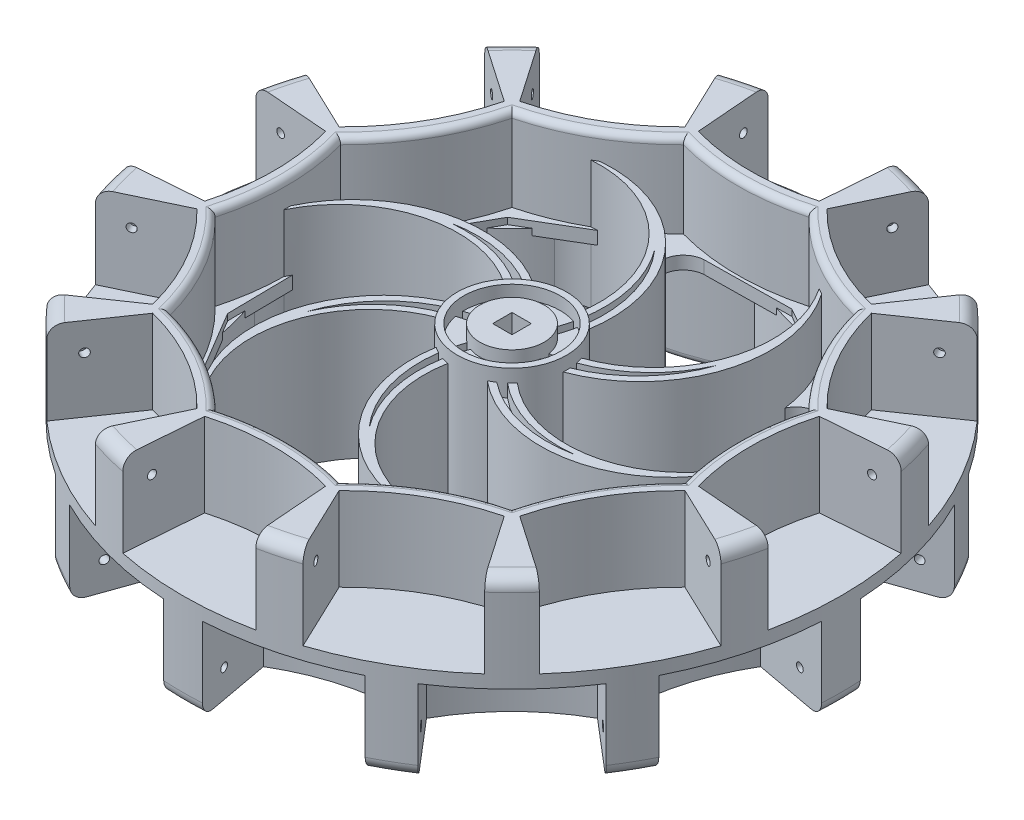
SolidWorks part; units mm, degrees
material "Nylon 101"
ref_plane "Front Plane" through (0, 0, 0) normal (0, 0, 1) x (1, 0, 0)
ref_plane "Top Plane" through (0, 0, 0) normal (0, 1, 0) x (1, 0, 0)
ref_plane "Right Plane" through (0, 0, 0) normal (1, 0, 0) x (0, 0, -1)
sketch "Sketch1" plane through (0, 0, 0) normal (0, 1, 0) x (1, 0, 0)
  line L1 (-28.2843, -28.2843) -> (-10.3528, -38.637) construction
  line L2 (-10.3528, -38.637) -> (10.3528, -38.637) construction
  line L3 (10.3528, -38.637) -> (28.2843, -28.2843) construction
  line L4 (28.2843, -28.2843) -> (38.637, -10.3528) construction
  line L5 (38.637, -10.3528) -> (38.637, 10.3528) construction
  line L6 (38.637, 10.3528) -> (28.2843, 28.2843) construction
  line L7 (28.2843, 28.2843) -> (10.3528, 38.637) construction
  line L8 (10.3528, 38.637) -> (-10.3528, 38.637) construction
  line L9 (-10.3528, 38.637) -> (-28.2843, 28.2843) construction
  line L10 (-28.2843, 28.2843) -> (-38.637, 10.3528) construction
  line L11 (-38.637, 10.3528) -> (-38.637, -10.3528) construction
  line L12 (-38.637, -10.3528) -> (-28.2843, -28.2843) construction
  circle A0 centre (0, 0) radius 38.637 construction
  arc A1 (38.637, 10.3528) -> (38.637, -10.3528) centre (71.5246, 0) ccw
  arc A2 (38.637, -10.3528) -> (28.2843, -28.2843) centre (61.9421, -35.7623) ccw
  arc A3 (28.2843, -28.2843) -> (10.3528, -38.637) centre (35.7623, -61.9421) ccw
  arc A4 (10.3528, -38.637) -> (-10.3528, -38.637) centre (0, -71.5246) ccw
  arc A5 (-10.3528, -38.637) -> (-28.2843, -28.2843) centre (-35.7623, -61.9421) ccw
  arc A6 (-28.2843, -28.2843) -> (-38.637, -10.3528) centre (-61.9421, -35.7623) ccw
  arc A7 (-38.637, -10.3528) -> (-38.637, 10.3528) centre (-71.5246, 0) ccw
  arc A8 (-38.637, 10.3528) -> (-28.2843, 28.2843) centre (-61.9421, 35.7623) ccw
  arc A9 (-28.2843, 28.2843) -> (-10.3528, 38.637) centre (-35.7623, 61.9421) ccw
  arc A10 (-10.3528, 38.637) -> (10.3528, 38.637) centre (0, 71.5246) ccw
  arc A11 (10.3528, 38.637) -> (28.2843, 28.2843) centre (35.7623, 61.9421) ccw
  arc A12 (28.2843, 28.2843) -> (38.637, 10.3528) centre (61.9421, 35.7623) ccw
  point P51 (0, 0)
  dimension "D2" = 34.4786
  dimension "D1" = 80
  dimension "D3" = 12
extrude "Boss-Extrude1" add sketch "Sketch1" along normal mid plane 28
sketch "Sketch3" plane through (0, 0, 0) normal (0, 1, 0) x (1, 0, 0)
  circle A0 centre (0, 0) radius 51.2
  dimension "D1" = 102.4
extrude "Boss-Extrude2" add sketch "Sketch3" along normal mid plane 2 contours A0
sketch "Sketch4" plane through (0, 14, 0) normal (0, 1, 0) x (1, 0, 0)
  arc A0 (9.7459, 36.372) -> (26.6262, 26.6262) centre (35.7623, 61.9421) ccw
  arc A1 (26.6262, 26.6262) -> (36.372, 9.7459) centre (61.9421, 35.7623) ccw
  arc A2 (36.372, 9.7459) -> (36.372, -9.7459) centre (71.5246, 0) ccw
  arc A3 (36.372, -9.7459) -> (26.6262, -26.6262) centre (61.9421, -35.7623) ccw
  arc A4 (26.6262, -26.6262) -> (9.7459, -36.372) centre (35.7623, -61.9421) ccw
  arc A5 (9.7459, -36.372) -> (-9.7459, -36.372) centre (0, -71.5246) ccw
  arc A6 (-9.7459, -36.372) -> (-26.6262, -26.6262) centre (-35.7623, -61.9421) ccw
  arc A7 (-26.6262, -26.6262) -> (-36.372, -9.7459) centre (-61.9421, -35.7623) ccw
  arc A8 (-36.372, -9.7459) -> (-36.372, 9.7459) centre (-71.5246, 0) ccw
  arc A9 (-36.372, 9.7459) -> (-26.6262, 26.6262) centre (-61.9421, 35.7623) ccw
  arc A10 (-26.6262, 26.6262) -> (-9.7459, 36.372) centre (-35.7623, 61.9421) ccw
  arc A11 (-9.7459, 36.372) -> (9.7459, 36.372) centre (0, 71.5246) ccw
  arc A12 (38.637, -10.3528) -> (28.2843, -28.2843) centre (61.9421, -35.7623) ccw
  arc A13 (38.637, 10.3528) -> (38.637, -10.3528) centre (71.5246, 0) ccw
  arc A14 (28.2843, 28.2843) -> (38.637, 10.3528) centre (61.9421, 35.7623) ccw
  arc A15 (10.3528, 38.637) -> (28.2843, 28.2843) centre (35.7623, 61.9421) ccw
  arc A16 (-10.3528, 38.637) -> (10.3528, 38.637) centre (0, 71.5246) ccw
  arc A17 (-28.2843, 28.2843) -> (-10.3528, 38.637) centre (-35.7623, 61.9421) ccw
  arc A18 (-38.637, 10.3528) -> (-28.2843, 28.2843) centre (-61.9421, 35.7623) ccw
  arc A19 (-38.637, -10.3528) -> (-38.637, 10.3528) centre (-71.5246, 0) ccw
  arc A20 (-28.2843, -28.2843) -> (-38.637, -10.3528) centre (-61.9421, -35.7623) ccw
  arc A21 (-10.3528, -38.637) -> (-28.2843, -28.2843) centre (-35.7623, -61.9421) ccw
  arc A22 (10.3528, -38.637) -> (-10.3528, -38.637) centre (0, -71.5246) ccw
  arc A23 (28.2843, -28.2843) -> (10.3528, -38.637) centre (35.7623, -61.9421) ccw
  arc A24 (38.637, -10.3528) -> (28.2843, -28.2843) centre (61.9421, -35.7623) ccw
  arc A25 (38.637, 10.3528) -> (38.637, -10.3528) centre (71.5246, 0) ccw
  arc A26 (28.2843, 28.2843) -> (38.637, 10.3528) centre (61.9421, 35.7623) ccw
  arc A27 (10.3528, 38.637) -> (28.2843, 28.2843) centre (35.7623, 61.9421) ccw
  arc A28 (-10.3528, 38.637) -> (10.3528, 38.637) centre (0, 71.5246) ccw
  arc A29 (-28.2843, 28.2843) -> (-10.3528, 38.637) centre (-35.7623, 61.9421) ccw
  arc A30 (-38.637, 10.3528) -> (-28.2843, 28.2843) centre (-61.9421, 35.7623) ccw
  arc A31 (-38.637, -10.3528) -> (-38.637, 10.3528) centre (-71.5246, 0) ccw
  arc A32 (-28.2843, -28.2843) -> (-38.637, -10.3528) centre (-61.9421, -35.7623) ccw
  arc A33 (-10.3528, -38.637) -> (-28.2843, -28.2843) centre (-35.7623, -61.9421) ccw
  arc A34 (10.3528, -38.637) -> (-10.3528, -38.637) centre (0, -71.5246) ccw
  arc A35 (28.2843, -28.2843) -> (10.3528, -38.637) centre (35.7623, -61.9421) ccw
  dimension "D1" = 0
  dimension "D2" = 2
extrude "Cut-Extrude1" cut sketch "Sketch4" against normal blind 4 contours A11 A10 A9 A8 A7 A6 A5 A4 A3 A2 A1 A0 region at (0, 14, 0)
mirror "Mirror1" about plane through (0, 0, 0) normal (0, 1, 0) of "Cut-Extrude1"
sketch "Sketch5" plane through (0, 10, 0) normal (0, 1, 0) x (1, 0, 0)
  circle A0 centre (0, 0) radius 5
  circle A1 centre (0, 0) radius 7.5
  circle A2 centre (0, 0) radius 8.5
  dimension "D1" = 10
  dimension "D2" = 15
  dimension "D3" = 1
extrude "Boss-Extrude3" add sketch "Sketch5" along normal blind 2 contours A2 A1 | A0 region at (0, 10, 0) region at (-8.2596, 10, 0)
mirror "Mirror2" about plane through (0, 0, 0) normal (0, 1, 0) of "Boss-Extrude3"
sketch "Sketch6" plane through (0, 12, 0) normal (0, 1, 0) x (1, 0, 0)
  line L1 (1.5, 1.5) -> (-1.5, 1.5)
  line L2 (1.5, 1.5) -> (1.5, -1.5)
  line L3 (1.5, -1.5) -> (-1.5, -1.5)
  line L4 (-1.5, 1.5) -> (-1.5, -1.5)
  line L5 (1.5, 1.5) -> (-1.5, -1.5) construction
  line L6 (1.5, -1.5) -> (-1.5, 1.5) construction
  point P0 (0, 0)
  dimension "D1" = 3
extrude "Cut-Extrude2" cut sketch "Sketch6" against normal through all
sketch "Sketch7" plane through (0, 10, 0) normal (0, 1, 0) x (1, 0, 0)
  line L1 (-3, -1.7321) -> (0, -3.4641) construction
  line L2 (0, -3.4641) -> (3, -1.7321) construction
  line L3 (3, -1.7321) -> (3, 1.7321) construction
  line L4 (3, 1.7321) -> (0, 3.4641) construction
  line L5 (0, 3.4641) -> (-3, 1.7321) construction
  line L6 (-3, 1.7321) -> (-3, -1.7321) construction
  circle A0 centre (0, 0) radius 3 construction
  circle A1 centre (0, 0) radius 8.5 construction
  arc A2 (6.4077, -5.5849) -> (5.7058, -6.3003) centre (0, 0) ccw
  circle A3 centre (0, 0) radius 5 construction
  arc A4 (4.6235, 1.9034) -> (7.3346, 37.8352) centre (1.8741, 20.179) ccw
  circle A5 centre (0, 0) radius 5
  arc A6 (4.7636, -1.5194) -> (7.3346, 37.8352) centre (1.4596, 18.4577) ccw
  arc A7 (3.9601, -3.0524) -> (36.4335, 12.5657) centre (18.4126, 8.4665) ccw
  arc A8 (1.066, -4.885) -> (36.4335, 12.5657) centre (16.7147, 7.9648) ccw
  arc A9 (-0.6634, -4.9558) -> (29.099, -25.2695) centre (16.5385, -11.7125) ccw
  arc A10 (-3.6976, -3.3657) -> (29.099, -25.2695) centre (15.2551, -10.4929) ccw
  arc A11 (-4.6235, -1.9034) -> (-7.3346, -37.8352) centre (-1.8741, -20.179) ccw
  arc A12 (-4.7636, 1.5194) -> (-7.3346, -37.8352) centre (-1.4596, -18.4577) ccw
  arc A13 (-3.9601, 3.0524) -> (-36.4335, -12.5657) centre (-18.4126, -8.4665) ccw
  arc A14 (-1.066, 4.885) -> (-36.4335, -12.5657) centre (-16.7147, -7.9648) ccw
  arc A15 (0.6634, 4.9558) -> (-29.099, 25.2695) centre (-16.5385, 11.7125) ccw
  arc A16 (3.6976, 3.3657) -> (-29.099, 25.2695) centre (-15.2551, 10.4929) ccw
  arc A17 (2.0852, -4.5444) -> (3.9056, -6.4029) centre (16.7147, 7.9648) ccw
  arc A18 (-10.3528, 38.637) -> (10.3528, 38.637) centre (0, 71.5246) ccw construction
  circle A19 centre (0, 0) radius 7.5 construction
  circle A20 centre (0, 0) radius 7.5
  arc A21 (2.0837, -2.1583) -> (2.1324, -2.2329) centre (18.4126, 8.4665) ccw
  arc A22 (0.8166, -2.8867) -> (0.8687, -2.9626) centre (16.7147, 7.9648) ccw
  arc A23 (-0.8273, -2.8837) -> (-0.8676, -2.9632) centre (16.5385, -11.7125) ccw
  arc A24 (-2.0917, -2.1506) -> (-2.1313, -2.2336) centre (15.2551, -10.4929) ccw
  arc A25 (-2.911, -0.7253) -> (-3, -0.7303) centre (-1.8741, -20.179) ccw
  arc A26 (-9.7459, 36.372) -> (9.7459, 36.372) centre (0, 71.5246) ccw
  arc A27 (-26.6262, 26.6262) -> (-9.7459, 36.372) centre (-35.7623, 61.9421) ccw
  arc A28 (-36.372, 9.7459) -> (-26.6262, 26.6262) centre (-61.9421, 35.7623) ccw
  arc A29 (-36.372, -9.7459) -> (-36.372, 9.7459) centre (-71.5246, 0) ccw
  arc A30 (-26.6262, -26.6262) -> (-36.372, -9.7459) centre (-61.9421, -35.7623) ccw
  arc A31 (-9.7459, -36.372) -> (-26.6262, -26.6262) centre (-35.7623, -61.9421) ccw
  arc A32 (9.7459, -36.372) -> (-9.7459, -36.372) centre (0, -71.5246) ccw
  arc A33 (26.6262, -26.6262) -> (9.7459, -36.372) centre (35.7623, -61.9421) ccw
  arc A34 (36.372, -9.7459) -> (26.6262, -26.6262) centre (61.9421, -35.7623) ccw
  arc A35 (36.372, 9.7459) -> (36.372, -9.7459) centre (71.5246, 0) ccw
  arc A36 (26.6262, 26.6262) -> (36.372, 9.7459) centre (61.9421, 35.7623) ccw
  arc A37 (9.7459, 36.372) -> (26.6262, 26.6262) centre (35.7623, 61.9421) ccw
  arc A38 (-9.7459, 36.372) -> (9.7459, 36.372) centre (0, 71.5246) ccw
  arc A39 (-26.6262, 26.6262) -> (-9.7459, 36.372) centre (-35.7623, 61.9421) ccw
  arc A40 (-36.372, 9.7459) -> (-26.6262, 26.6262) centre (-61.9421, 35.7623) ccw
  arc A41 (-36.372, -9.7459) -> (-36.372, 9.7459) centre (-71.5246, 0) ccw
  arc A42 (-26.6262, -26.6262) -> (-36.372, -9.7459) centre (-61.9421, -35.7623) ccw
  arc A43 (-9.7459, -36.372) -> (-26.6262, -26.6262) centre (-35.7623, -61.9421) ccw
  arc A44 (9.7459, -36.372) -> (-9.7459, -36.372) centre (0, -71.5246) ccw
  arc A45 (26.6262, -26.6262) -> (9.7459, -36.372) centre (35.7623, -61.9421) ccw
  arc A46 (36.372, -9.7459) -> (26.6262, -26.6262) centre (61.9421, -35.7623) ccw
  arc A47 (36.372, 9.7459) -> (36.372, -9.7459) centre (71.5246, 0) ccw
  arc A48 (26.6262, 26.6262) -> (36.372, 9.7459) centre (61.9421, 35.7623) ccw
  arc A49 (9.7459, 36.372) -> (26.6262, 26.6262) centre (35.7623, 61.9421) ccw
  arc A50 (-2.9083, 0.7361) -> (-3, 0.729) centre (-1.4596, -18.4577) ccw
  arc A51 (-2.0837, 2.1583) -> (-2.1324, 2.2329) centre (-18.4126, -8.4665) ccw
  arc A52 (-0.8166, 2.8867) -> (-0.8687, 2.9626) centre (-16.7147, -7.9648) ccw
  arc A53 (0.8273, 2.8837) -> (0.8676, 2.9632) centre (-16.5385, 11.7125) ccw
  arc A54 (2.0917, 2.1506) -> (2.1313, 2.2336) centre (-15.2551, 10.4929) ccw
  arc A55 (2.911, 0.7253) -> (3, 0.7303) centre (1.8741, 20.179) ccw
  arc A56 (2.9083, -0.7361) -> (3, -0.729) centre (1.4596, 18.4577) ccw
  arc A57 (4.7061, -7.0783) -> (20.5551, -10.8967) centre (16.7147, 7.9648) ccw
  arc A58 (-0.0486, -1.4954) -> (20.5551, -10.8967) centre (16.7147, 7.9648) ccw construction
  arc A59 (5.7058, -6.3003) -> (20.5551, -10.8967) centre (18.4126, 8.4665) ccw
  arc A60 (1.2708, -0.7898) -> (20.5551, -10.8967) centre (18.4126, 8.4665) ccw construction
  arc A61 (3.2664, -3.7856) -> (4.9608, -5.625) centre (18.4126, 8.4665) ccw
  arc A62 (1.2708, -0.7898) -> (19.7143, 12.3529) centre (1.4596, 18.4577) ccw construction
  arc A63 (-0.0486, -1.4954) -> (0.8408, -23.2495) centre (16.5385, -11.7125) ccw construction
  arc A64 (-1.3194, -0.7056) -> (0.8408, -23.2495) centre (15.2551, -10.4929) ccw construction
  arc A65 (-1.3194, -0.7056) -> (-19.7143, -12.3529) centre (-1.8741, -20.179) ccw construction
  arc A66 (-1.2708, 0.7898) -> (-19.7143, -12.3529) centre (-1.4596, -18.4577) ccw construction
  arc A67 (-1.2708, 0.7898) -> (-20.5551, 10.8967) centre (-18.4126, -8.4665) ccw construction
  arc A68 (0.0486, 1.4954) -> (-20.5551, 10.8967) centre (-16.7147, -7.9648) ccw construction
  arc A69 (0.0486, 1.4954) -> (-0.8408, 23.2495) centre (-16.5385, 11.7125) ccw construction
  arc A70 (1.3194, 0.7056) -> (-0.8408, 23.2495) centre (-15.2551, 10.4929) ccw construction
  arc A71 (1.3194, 0.7056) -> (19.7143, 12.3529) centre (1.8741, 20.179) ccw construction
  arc A72 (3, -1.7321) -> (36.4335, 12.5657) centre (18.4126, 8.4665) ccw construction
  arc A73 (3, -1.7321) -> (7.3346, 37.8352) centre (1.4596, 18.4577) ccw construction
  arc A74 (4.9782, -0.4664) -> (7.4978, 0.1809) centre (1.4596, 18.4577) ccw
  arc A75 (4.9116, 0.936) -> (7.3518, 1.4837) centre (1.8741, 20.179) ccw
  arc A76 (3, 1.7321) -> (7.3346, 37.8352) centre (1.8741, 20.179) ccw construction
  arc A77 (3, 1.7321) -> (-29.099, 25.2695) centre (-15.2551, 10.4929) ccw construction
  arc A78 (2.893, 4.078) -> (3.5923, 6.5837) centre (-15.2551, 10.4929) ccw
  arc A79 (1.6452, 4.7216) -> (2.391, 7.1087) centre (-16.5385, 11.7125) ccw
  arc A80 (0, 3.4641) -> (-29.099, 25.2695) centre (-16.5385, 11.7125) ccw construction
  arc A81 (0, 3.4641) -> (-36.4335, -12.5657) centre (-16.7147, -7.9648) ccw construction
  arc A82 (-2.0852, 4.5444) -> (-3.9056, 6.4029) centre (-16.7147, -7.9648) ccw
  arc A83 (-3.2664, 3.7856) -> (-4.9608, 5.625) centre (-18.4126, -8.4665) ccw
  arc A84 (-3, 1.7321) -> (-36.4335, -12.5657) centre (-18.4126, -8.4665) ccw construction
  arc A85 (-3, 1.7321) -> (-7.3346, -37.8352) centre (-1.4596, -18.4577) ccw construction
  arc A86 (-4.9782, 0.4664) -> (-7.4978, -0.1809) centre (-1.4596, -18.4577) ccw
  arc A87 (-4.9116, -0.936) -> (-7.3518, -1.4837) centre (-1.8741, -20.179) ccw
  arc A88 (-3, -1.7321) -> (-7.3346, -37.8352) centre (-1.8741, -20.179) ccw construction
  arc A89 (-3, -1.7321) -> (29.099, -25.2695) centre (15.2551, -10.4929) ccw construction
  arc A90 (-2.893, -4.078) -> (-3.5923, -6.5837) centre (15.2551, -10.4929) ccw
  arc A91 (-1.6452, -4.7216) -> (-2.391, -7.1087) centre (16.5385, -11.7125) ccw
  arc A92 (0, -3.4641) -> (29.099, -25.2695) centre (16.5385, -11.7125) ccw construction
  arc A93 (0, -3.4641) -> (36.4335, 12.5657) centre (16.7147, 7.9648) ccw construction
  arc A94 (-2.6033, -8.0915) -> (0.8408, -23.2495) centre (16.5385, -11.7125) ccw
  arc A95 (-3.777, -7.6147) -> (0.8408, -23.2495) centre (15.2551, -10.4929) ccw
  arc A96 (-8.3091, -1.7912) -> (-19.7143, -12.3529) centre (-1.8741, -20.179) ccw
  arc A97 (-8.4831, -0.5364) -> (-19.7143, -12.3529) centre (-1.4596, -18.4577) ccw
  arc A98 (-5.7058, 6.3003) -> (-20.5551, 10.8967) centre (-18.4126, -8.4665) ccw
  arc A99 (-4.7061, 7.0783) -> (-20.5551, 10.8967) centre (-16.7147, -7.9648) ccw
  arc A100 (2.6033, 8.0915) -> (-0.8408, 23.2495) centre (-16.5385, 11.7125) ccw
  arc A101 (3.777, 7.6147) -> (-0.8408, 23.2495) centre (-15.2551, 10.4929) ccw
  arc A102 (8.3091, 1.7912) -> (19.7143, 12.3529) centre (1.8741, 20.179) ccw
  arc A103 (8.4831, 0.5364) -> (19.7143, 12.3529) centre (1.4596, 18.4577) ccw
  point P42 (0, 0)
  arc M27 (9.7459, 36.372) -> (-9.7459, 36.372) centre (0, 71.5246) cw
  arc M28 (-9.7459, 36.372) -> (-26.6262, 26.6262) centre (-35.7623, 61.9421) cw
  arc M29 (-26.6262, 26.6262) -> (-36.372, 9.7459) centre (-61.9421, 35.7623) cw
  arc M30 (-36.372, 9.7459) -> (-36.372, -9.7459) centre (-71.5246, 0) cw
  arc M31 (-36.372, -9.7459) -> (-26.6262, -26.6262) centre (-61.9421, -35.7623) cw
  arc M32 (-26.6262, -26.6262) -> (-9.7459, -36.372) centre (-35.7623, -61.9421) cw
  arc M33 (-9.7459, -36.372) -> (9.7459, -36.372) centre (0, -71.5246) cw
  arc M34 (9.7459, -36.372) -> (26.6262, -26.6262) centre (35.7623, -61.9421) cw
  arc M35 (26.6262, -26.6262) -> (36.372, -9.7459) centre (61.9421, -35.7623) cw
  arc M36 (36.372, -9.7459) -> (36.372, 9.7459) centre (71.5246, 0) cw
  arc M37 (36.372, 9.7459) -> (26.6262, 26.6262) centre (61.9421, 35.7623) cw
  arc M38 (26.6262, 26.6262) -> (9.7459, 36.372) centre (35.7623, 61.9421) cw
  dimension "D1" = 6
  dimension "D4" = 18.4813
  dimension "D6" = 20.2485
  dimension "D5" = 7.3346
  dimension "D3" = 0
  dimension "D7" = 1
  dimension "D2" = 6
extrude "Cut-Extrude3" cut sketch "Sketch7" against normal through all contours A2 A7 A6 M36 M37 M38 | A16 A2 A4 M38 M27 M28 | A2 A15 A14 M28 M29 M30 | A2 A13 A12 M30 M31 M32 | A2 A11 A10 M32 M33 M34 | A2 A9 A8 M34 M35 M36 region at (23.4877, 10, -4.9843) region at (7.4273, 10, -22.8331) region at (16.0604, 10, 17.8487) region at (-16.0604, 10, -17.8487) region at (-7.4273, 10, 22.8331) region at (-23.4877, 10, 4.9843)
sketch "Sketch8" plane through (0, 0, 0) normal (0, 1, 0) x (1, 0, 0)
  arc A0 (9.7459, 36.372) -> (26.6262, 26.6262) centre (35.7623, 61.9421) ccw construction
  arc A1 (18.066, 30.0434) -> (24.1038, 27.3767) centre (35.7623, 61.9421) ccw
  arc A2 (8.4832, -0.5335) -> (18.066, 30.0434) centre (1.4596, 18.4577) ccw construction
  arc A3 (20.873, 24.2127) -> (18.066, 30.0434) centre (1.4596, 18.4577) ccw
  arc A4 (20.873, 24.2127) -> (24.1038, 27.3767) centre (24.0705, 24.1793) cw
  arc A5 (31.4053, -5.9702) -> (35.0514, -0.6239) centre (16.7147, 7.9648) ccw
  arc A6 (31.4053, -5.9702) -> (35.7609, -7.1862) centre (32.9751, -8.756) cw
  arc A7 (35.0514, -0.6239) -> (35.7609, -7.1862) centre (71.5246, 0) ccw
  arc A8 (10.5323, -30.1829) -> (16.9853, -30.6673) centre (15.2551, -10.4929) ccw
  arc A9 (10.5323, -30.1829) -> (11.657, -34.5629) centre (8.9047, -32.9353) cw
  arc A10 (16.9853, -30.6673) -> (11.657, -34.5629) centre (35.7623, -61.9421) ccw
  arc A11 (-20.873, -24.2127) -> (-18.066, -30.0434) centre (-1.4596, -18.4577) ccw
  arc A12 (-20.873, -24.2127) -> (-24.1038, -27.3767) centre (-24.0705, -24.1793) cw
  arc A13 (-18.066, -30.0434) -> (-24.1038, -27.3767) centre (-35.7623, -61.9421) ccw
  arc A14 (-31.4053, 5.9702) -> (-35.0514, 0.6239) centre (-16.7147, -7.9648) ccw
  arc A15 (-31.4053, 5.9702) -> (-35.7609, 7.1862) centre (-32.9751, 8.756) cw
  arc A16 (-35.0514, 0.6239) -> (-35.7609, 7.1862) centre (-71.5246, 0) ccw
  arc A17 (-10.5323, 30.1829) -> (-16.9853, 30.6673) centre (-15.2551, 10.4929) ccw
  arc A18 (-10.5323, 30.1829) -> (-11.657, 34.5629) centre (-8.9047, 32.9353) cw
  arc A19 (-16.9853, 30.6673) -> (-11.657, 34.5629) centre (-35.7623, 61.9421) ccw
  point P43 (0, 0)
  dimension "D1" = 3.1976
  dimension "D3" = 24.1793
  dimension "D2" = 34.1178
  dimension "D4" = 6
extrude "Boss-Extrude4" add sketch "Sketch8" along normal mid plane 2
sketch "Sketch9" plane through (0, 10, 0) normal (0, 1, 0) x (1, 0, 0)
  arc A0 (3.1747, -3.8628) -> (20.4014, -10.7753) centre (18.1668, 8.5774) ccw
  arc A1 (2.0501, -4.5604) -> (20.4014, -10.7753) centre (16.561, 8.0862) ccw
  circle A2 centre (0, 0) radius 5 construction
  arc A3 (2.0501, -4.5604) -> (3.1747, -3.8628) centre (0, 0) ccw
  arc A4 (3.7796, -7.6135) -> (6.4077, -5.5849) centre (0, 0) ccw
  arc A5 (3.7796, -7.6135) -> (35.0514, -0.6239) centre (16.7147, 7.9648) ccw
  arc A6 (35.0484, 0.4161) -> (35.0514, -0.6239) centre (71.5246, 0) ccw
  arc A7 (6.4077, -5.5849) -> (35.0484, 0.4161) centre (18.4126, 8.4665) ccw
  arc A8 (4.7061, -7.0783) -> (5.6498, -6.3506) centre (0, 0) ccw
  circle A9 centre (0, 0) radius 7.5 construction
  arc A10 (35.0484, 0.4161) -> (35.0514, -0.6239) centre (71.5246, 0) ccw
  arc A11 (3.896, -6.4087) -> (4.8942, -5.683) centre (0, 0) ccw
  arc A12 (-1.7579, -4.6808) -> (0.8691, -23.0558) centre (16.5117, -11.4442) ccw
  arc A14 (-2.9244, -4.0556) -> (0.8691, -23.0558) centre (15.2834, -10.2992) ccw
  arc A15 (-3.6021, -6.5784) -> (-2.4745, -7.08) centre (0, 0) ccw
  arc A16 (-3.777, -7.6147) -> (-2.6749, -8.0682) centre (0, 0) ccw
  arc A17 (-2.9244, -4.0556) -> (-1.7579, -4.6808) centre (0, 0) ccw
  arc A18 (-4.9326, -0.818) -> (-19.5324, -12.2805) centre (-1.6552, -20.0216) ccw
  arc A19 (-4.9745, 0.5048) -> (-19.5324, -12.2805) centre (-1.2777, -18.3854) ccw
  arc A20 (-7.4981, -0.1697) -> (-7.3687, -1.397) centre (0, 0) ccw
  arc A21 (-8.4831, -0.5364) -> (-8.3247, -1.7176) centre (0, 0) ccw
  arc A22 (-4.9745, 0.5048) -> (-4.9326, -0.818) centre (0, 0) ccw
  arc A23 (-3.1747, 3.8628) -> (-20.4014, 10.7753) centre (-18.1668, -8.5774) ccw
  arc A24 (-2.0501, 4.5604) -> (-20.4014, 10.7753) centre (-16.561, -8.0862) ccw
  arc A25 (-3.896, 6.4087) -> (-4.8942, 5.683) centre (0, 0) ccw
  arc A26 (-4.7061, 7.0783) -> (-5.6498, 6.3506) centre (0, 0) ccw
  arc A27 (-2.0501, 4.5604) -> (-3.1747, 3.8628) centre (0, 0) ccw
  arc A28 (1.7579, 4.6808) -> (-0.8691, 23.0558) centre (-16.5117, 11.4442) ccw
  arc A29 (2.9244, 4.0556) -> (-0.8691, 23.0558) centre (-15.2834, 10.2992) ccw
  arc A30 (3.6021, 6.5784) -> (2.4745, 7.08) centre (0, 0) ccw
  arc A31 (3.777, 7.6147) -> (2.6749, 8.0682) centre (0, 0) ccw
  arc A32 (2.9244, 4.0556) -> (1.7579, 4.6808) centre (0, 0) ccw
  arc A33 (4.9326, 0.818) -> (19.5324, 12.2805) centre (1.6552, 20.0216) ccw
  arc A34 (4.9745, -0.5048) -> (19.5324, 12.2805) centre (1.2777, 18.3854) ccw
  arc A35 (7.4981, 0.1697) -> (7.3687, 1.397) centre (0, 0) ccw
  arc A36 (8.4831, 0.5364) -> (8.3247, 1.7176) centre (0, 0) ccw
  arc A37 (4.9745, -0.5048) -> (4.9326, 0.818) centre (0, 0) ccw
  point P67 (0, 0)
  arc M5 (6.4077, -5.5849) -> (3.7796, -7.6135) centre (0, 0) cw
  dimension "D1" = 0
  dimension "D2" = 6
extrude "Cut-Extrude4" cut sketch "Sketch9" against normal blind 2 contours A1 A0 M5 | A1 A11 A0 A3 | A17 A14 A15 A12 | A16 A14 A12 | A22 A19 A20 A18 | A21 A19 A18 | A27 A24 A25 A23 | A26 A24 A23 | A32 A29 A30 A28 | A31 A29 A28 | A37 A34 A35 A33 | A36 A34 A33 region at (3.4846, 10, 5.1553) region at (10.1165, 10, 9.2087) region at (-2.7223, 10, 5.5954) region at (-2.9167, 10, 13.3655) region at (-6.2069, 10, 0.4401) region at (-13.0332, 10, 4.1568) region at (-3.4846, 10, -5.1553) region at (-10.1165, 10, -9.2087) region at (2.7223, 10, -5.5954) region at (2.9167, 10, -13.3655) region at (6.2069, 10, -0.4401) region at (13.0332, 10, -4.1568)
mirror "Mirror3" about plane through (0, 0, 0) normal (0, 1, 0) of "Cut-Extrude4"
sketch "Sketch10" plane through (0, 14, 0) normal (0, 1, 0) x (1, 0, 0)
  line L0 (38.3506, 9.3947) -> (50.1469, 10.331)
  line L1 (0, 0) -> (68.0843, 18.2431) construction
  line L2 (37.9099, 11.0393) -> (48.594, 16.1265)
  line L3 (38.3506, -9.3947) -> (50.1469, -10.331)
  line L4 (37.9099, -11.0393) -> (48.594, -16.1265)
  line L5 (28.5153, -27.3113) -> (38.263, -34.0203)
  line L6 (27.3113, -28.5153) -> (34.0203, -38.263)
  line L7 (11.0393, -37.9099) -> (16.1265, -48.594)
  line L8 (9.3947, -38.3506) -> (10.331, -50.1469)
  line L9 (-9.3947, -38.3506) -> (-10.331, -50.1469)
  line L10 (-11.0393, -37.9099) -> (-16.1265, -48.594)
  line L11 (-27.3113, -28.5153) -> (-34.0203, -38.263)
  line L12 (-28.5153, -27.3113) -> (-38.263, -34.0203)
  line L13 (-37.9099, -11.0393) -> (-48.594, -16.1265)
  line L14 (-38.3506, -9.3947) -> (-50.1469, -10.331)
  line L15 (-38.3506, 9.3947) -> (-50.1469, 10.331)
  line L16 (-37.9099, 11.0393) -> (-48.594, 16.1265)
  line L17 (-28.5153, 27.3113) -> (-38.263, 34.0203)
  line L18 (-27.3113, 28.5153) -> (-34.0203, 38.263)
  line L19 (-11.0393, 37.9099) -> (-16.1265, 48.594)
  line L20 (-9.3947, 38.3506) -> (-10.331, 50.1469)
  line L21 (9.3947, 38.3506) -> (10.331, 50.1469)
  line L22 (11.0393, 37.9099) -> (16.1265, 48.594)
  line L23 (27.3113, 28.5153) -> (34.0203, 38.263)
  line L24 (28.5153, 27.3113) -> (38.263, 34.0203)
  circle A0 centre (0, 0) radius 51.2 construction
  circle A1 centre (0, 0) radius 51.2
  arc A12 (38.637, -10.3528) -> (28.2843, -28.2843) centre (61.9421, -35.7623) ccw
  arc A13 (38.637, 10.3528) -> (38.637, -10.3528) centre (71.5246, 0) ccw
  arc A14 (28.2843, 28.2843) -> (38.637, 10.3528) centre (61.9421, 35.7623) ccw
  arc A15 (10.3528, 38.637) -> (28.2843, 28.2843) centre (35.7623, 61.9421) ccw
  arc A16 (-10.3528, 38.637) -> (10.3528, 38.637) centre (0, 71.5246) ccw
  arc A17 (-28.2843, 28.2843) -> (-10.3528, 38.637) centre (-35.7623, 61.9421) ccw
  arc A18 (-38.637, 10.3528) -> (-28.2843, 28.2843) centre (-61.9421, 35.7623) ccw
  arc A19 (-38.637, -10.3528) -> (-38.637, 10.3528) centre (-71.5246, 0) ccw
  arc A20 (-28.2843, -28.2843) -> (-38.637, -10.3528) centre (-61.9421, -35.7623) ccw
  arc A21 (-10.3528, -38.637) -> (-28.2843, -28.2843) centre (-35.7623, -61.9421) ccw
  arc A22 (10.3528, -38.637) -> (-10.3528, -38.637) centre (0, -71.5246) ccw
  arc A23 (28.2843, -28.2843) -> (10.3528, -38.637) centre (35.7623, -61.9421) ccw
  arc A24 (38.637, -10.3528) -> (28.2843, -28.2843) centre (61.9421, -35.7623) ccw
  arc A25 (38.637, 10.3528) -> (38.637, -10.3528) centre (71.5246, 0) ccw
  arc A26 (28.2843, 28.2843) -> (38.637, 10.3528) centre (61.9421, 35.7623) ccw
  arc A27 (10.3528, 38.637) -> (28.2843, 28.2843) centre (35.7623, 61.9421) ccw
  arc A28 (-10.3528, 38.637) -> (10.3528, 38.637) centre (0, 71.5246) ccw
  arc A29 (-28.2843, 28.2843) -> (-10.3528, 38.637) centre (-35.7623, 61.9421) ccw
  arc A30 (-38.637, 10.3528) -> (-28.2843, 28.2843) centre (-61.9421, 35.7623) ccw
  arc A31 (-38.637, -10.3528) -> (-38.637, 10.3528) centre (-71.5246, 0) ccw
  arc A32 (-28.2843, -28.2843) -> (-38.637, -10.3528) centre (-61.9421, -35.7623) ccw
  arc A33 (-10.3528, -38.637) -> (-28.2843, -28.2843) centre (-35.7623, -61.9421) ccw
  arc A34 (10.3528, -38.637) -> (-10.3528, -38.637) centre (0, -71.5246) ccw
  arc A35 (28.2843, -28.2843) -> (10.3528, -38.637) centre (35.7623, -61.9421) ccw
  point P79 (0, 0)
  arc M15 (28.2843, -28.2843) -> (38.637, -10.3528) centre (61.9421, -35.7623) cw
  arc M16 (38.637, -10.3528) -> (38.637, 10.3528) centre (71.5246, 0) cw
  arc M17 (38.637, 10.3528) -> (28.2843, 28.2843) centre (61.9421, 35.7623) cw
  arc M18 (28.2843, 28.2843) -> (10.3528, 38.637) centre (35.7623, 61.9421) cw
  arc M19 (10.3528, 38.637) -> (-10.3528, 38.637) centre (0, 71.5246) cw
  arc M20 (-10.3528, 38.637) -> (-28.2843, 28.2843) centre (-35.7623, 61.9421) cw
  arc M21 (-28.2843, 28.2843) -> (-38.637, 10.3528) centre (-61.9421, 35.7623) cw
  arc M22 (-38.637, 10.3528) -> (-38.637, -10.3528) centre (-71.5246, 0) cw
  arc M23 (-38.637, -10.3528) -> (-28.2843, -28.2843) centre (-61.9421, -35.7623) cw
  arc M24 (-28.2843, -28.2843) -> (-10.3528, -38.637) centre (-35.7623, -61.9421) cw
  arc M25 (-10.3528, -38.637) -> (10.3528, -38.637) centre (0, -71.5246) cw
  arc M26 (10.3528, -38.637) -> (28.2843, -28.2843) centre (35.7623, -61.9421) cw
  dimension "D2" = 1
  dimension "D3" = 3
  dimension "D4" = 12
  dimension "D1" = 0
extrude "Boss-Extrude5" add sketch "Sketch10" against normal up to surface (13 mm away) contours L24 A1 L23 M18 M17 | L22 A1 L21 M19 M18 | L20 A1 L19 M20 M19 | L18 A1 L17 M21 M20 | L16 A1 L15 M22 M21 | L14 A1 L13 M23 M22 | L12 A1 L11 M24 M23 | L10 A1 L9 M25 M24 | L8 A1 L7 M26 M25 | L6 A1 L5 M15 M26 | L4 A1 L3 M16 M15 | L1 L0 A1 M16 | L1 A1 L2 M17 region at (45.1731, 14, -10.9954) region at (44.6188, 14, -13.0643) region at (44.896, 14, 12.0298) region at (32.8661, 14, -32.8661) region at (32.8661, 14, 32.8661) region at (12.0298, 14, -44.896) region at (12.0298, 14, 44.896) region at (-12.0298, 14, -44.896) region at (-12.0298, 14, 44.896) region at (-32.8661, 14, -32.8661) region at (-32.8661, 14, 32.8661) region at (-44.896, 14, -12.0298) region at (-44.896, 14, 12.0298) up to face at (0, 1, 51.2)
sketch "Sketch11" plane through (0, 0, 0) normal (0, 1, 0) x (1, 0, 0)
  line L48 (33.761, -20.475) -> (42.7643, -28.1541)
  line L49 (45.7643, -22.9579) -> (34.6123, -19.0004)
  line L50 (39.4754, -0.8513) -> (51.112, -3)
  line L51 (51.112, 3) -> (39.4754, 0.8513)
  line L52 (34.6123, 19.0004) -> (45.7643, 22.9579)
  line L53 (42.7643, 28.1541) -> (33.761, 20.475)
  line L54 (20.475, 33.761) -> (28.1541, 42.7643)
  line L55 (22.9579, 45.7643) -> (19.0004, 34.6123)
  line L56 (0.8513, 39.4754) -> (3, 51.112)
  line L57 (-3, 51.112) -> (-0.8513, 39.4754)
  line L58 (-19.0004, 34.6123) -> (-22.9579, 45.7643)
  line L59 (-28.1541, 42.7643) -> (-20.475, 33.761)
  line L60 (-33.761, 20.475) -> (-42.7643, 28.1541)
  line L61 (-45.7643, 22.9579) -> (-34.6123, 19.0004)
  line L62 (-39.4754, 0.8513) -> (-51.112, 3)
  line L63 (-51.112, -3) -> (-39.4754, -0.8513)
  line L64 (-34.6123, -19.0004) -> (-45.7643, -22.9579)
  line L65 (-42.7643, -28.1541) -> (-33.761, -20.475)
  line L66 (-20.475, -33.761) -> (-28.1541, -42.7643)
  line L67 (-22.9579, -45.7643) -> (-19.0004, -34.6123)
  line L68 (-0.8513, -39.4754) -> (-3, -51.112)
  line L69 (3, -51.112) -> (0.8513, -39.4754)
  line L70 (19.0004, -34.6123) -> (22.9579, -45.7643)
  line L71 (28.1541, -42.7643) -> (20.475, -33.761)
  arc A12 (32.6103, 18.8275) -> (37.6551, 0) centre (69.0874, 18.5119) ccw
  arc A13 (18.8275, 32.6103) -> (32.6103, 18.8275) centre (50.5755, 50.5755) ccw
  arc A14 (0, 37.6551) -> (18.8275, 32.6103) centre (18.5119, 69.0874) ccw
  arc A15 (-18.8275, 32.6103) -> (0, 37.6551) centre (-18.5119, 69.0874) ccw
  arc A16 (-32.6103, 18.8275) -> (-18.8275, 32.6103) centre (-50.5755, 50.5755) ccw
  arc A17 (-37.6551, 0) -> (-32.6103, 18.8275) centre (-69.0874, 18.5119) ccw
  arc A18 (-32.6103, -18.8275) -> (-37.6551, 0) centre (-69.0874, -18.5119) ccw
  arc A19 (-18.8275, -32.6103) -> (-32.6103, -18.8275) centre (-50.5755, -50.5755) ccw
  arc A20 (0, -37.6551) -> (-18.8275, -32.6103) centre (-18.5119, -69.0874) ccw
  arc A21 (18.8275, -32.6103) -> (0, -37.6551) centre (18.5119, -69.0874) ccw
  arc A22 (32.6103, -18.8275) -> (18.8275, -32.6103) centre (50.5755, -50.5755) ccw
  arc A23 (37.6551, 0) -> (32.6103, -18.8275) centre (69.0874, -18.5119) ccw
  arc A48 (33.761, -20.475) -> (20.475, -33.761) centre (50.5755, -50.5755) ccw
  arc A49 (42.7643, -28.1541) -> (45.7643, -22.9579) centre (0, 0) ccw
  arc A50 (39.4754, -0.8513) -> (34.6123, -19.0004) centre (69.0874, -18.5119) ccw
  arc A51 (51.112, -3) -> (51.112, 3) centre (0, 0) ccw
  arc A52 (34.6123, 19.0004) -> (39.4754, 0.8513) centre (69.0874, 18.5119) ccw
  arc A53 (45.7643, 22.9579) -> (42.7643, 28.1541) centre (0, 0) ccw
  arc A54 (20.475, 33.761) -> (33.761, 20.475) centre (50.5755, 50.5755) ccw
  arc A55 (28.1541, 42.7643) -> (22.9579, 45.7643) centre (0, 0) ccw
  arc A56 (0.8513, 39.4754) -> (19.0004, 34.6123) centre (18.5119, 69.0874) ccw
  arc A57 (3, 51.112) -> (-3, 51.112) centre (0, 0) ccw
  arc A58 (-19.0004, 34.6123) -> (-0.8513, 39.4754) centre (-18.5119, 69.0874) ccw
  arc A59 (-22.9579, 45.7643) -> (-28.1541, 42.7643) centre (0, 0) ccw
  arc A60 (-33.761, 20.475) -> (-20.475, 33.761) centre (-50.5755, 50.5755) ccw
  arc A61 (-42.7643, 28.1541) -> (-45.7643, 22.9579) centre (0, 0) ccw
  arc A62 (-39.4754, 0.8513) -> (-34.6123, 19.0004) centre (-69.0874, 18.5119) ccw
  arc A63 (-51.112, 3) -> (-51.112, -3) centre (0, 0) ccw
  arc A64 (-34.6123, -19.0004) -> (-39.4754, -0.8513) centre (-69.0874, -18.5119) ccw
  arc A65 (-45.7643, -22.9579) -> (-42.7643, -28.1541) centre (0, 0) ccw
  arc A66 (-20.475, -33.761) -> (-33.761, -20.475) centre (-50.5755, -50.5755) ccw
  arc A67 (-28.1541, -42.7643) -> (-22.9579, -45.7643) centre (0, 0) ccw
  arc A68 (-0.8513, -39.4754) -> (-19.0004, -34.6123) centre (-18.5119, -69.0874) ccw
  arc A69 (-3, -51.112) -> (3, -51.112) centre (0, 0) ccw
  arc A70 (19.0004, -34.6123) -> (0.8513, -39.4754) centre (18.5119, -69.0874) ccw
  arc A71 (22.9579, -45.7643) -> (28.1541, -42.7643) centre (0, 0) ccw
sketch "Sketch13" plane through (0, -14, 0) normal (0, -1, 0) x (1, 0, 0)
  arc A0 (26.6262, 26.6262) -> (36.372, 9.7459) centre (61.9421, 35.7623) ccw construction
  arc A1 (9.7459, 36.372) -> (26.6262, 26.6262) centre (35.7623, 61.9421) ccw construction
  arc A2 (-9.7459, 36.372) -> (9.7459, 36.372) centre (0, 71.5246) ccw construction
  arc A3 (-26.6262, 26.6262) -> (-9.7459, 36.372) centre (-35.7623, 61.9421) ccw construction
  arc A4 (-36.372, 9.7459) -> (-26.6262, 26.6262) centre (-61.9421, 35.7623) ccw construction
  arc A5 (-36.372, -9.7459) -> (-36.372, 9.7459) centre (-71.5246, 0) ccw construction
  arc A6 (-26.6262, -26.6262) -> (-36.372, -9.7459) centre (-61.9421, -35.7623) ccw construction
  arc A7 (-9.7459, -36.372) -> (-26.6262, -26.6262) centre (-35.7623, -61.9421) ccw construction
  arc A8 (9.7459, -36.372) -> (-9.7459, -36.372) centre (0, -71.5246) ccw construction
  arc A9 (26.6262, -26.6262) -> (9.7459, -36.372) centre (35.7623, -61.9421) ccw construction
  arc A10 (36.372, -9.7459) -> (26.6262, -26.6262) centre (61.9421, -35.7623) ccw construction
  arc A11 (36.372, 9.7459) -> (36.372, -9.7459) centre (71.5246, 0) ccw construction
  arc A12 (28.2843, 28.2843) -> (38.637, 10.3528) centre (61.9421, 35.7623) ccw
  arc A13 (10.3528, 38.637) -> (28.2843, 28.2843) centre (35.7623, 61.9421) ccw
  arc A14 (-10.3528, 38.637) -> (10.3528, 38.637) centre (0, 71.5246) ccw
  arc A15 (-28.2843, 28.2843) -> (-10.3528, 38.637) centre (-35.7623, 61.9421) ccw
  arc A16 (-38.637, 10.3528) -> (-28.2843, 28.2843) centre (-61.9421, 35.7623) ccw
  arc A17 (-38.637, -10.3528) -> (-38.637, 10.3528) centre (-71.5246, 0) ccw
  arc A18 (-28.2843, -28.2843) -> (-38.637, -10.3528) centre (-61.9421, -35.7623) ccw
  arc A19 (-10.3528, -38.637) -> (-28.2843, -28.2843) centre (-35.7623, -61.9421) ccw
  arc A20 (10.3528, -38.637) -> (-10.3528, -38.637) centre (0, -71.5246) ccw
  arc A21 (28.2843, -28.2843) -> (10.3528, -38.637) centre (35.7623, -61.9421) ccw
  arc A22 (38.637, -10.3528) -> (28.2843, -28.2843) centre (61.9421, -35.7623) ccw
  arc A23 (38.637, 10.3528) -> (38.637, -10.3528) centre (71.5246, 0) ccw
  arc A24 (28.2843, 28.2843) -> (38.637, 10.3528) centre (61.9421, 35.7623) ccw
  arc A25 (10.3528, 38.637) -> (28.2843, 28.2843) centre (35.7623, 61.9421) ccw
  arc A26 (-10.3528, 38.637) -> (10.3528, 38.637) centre (0, 71.5246) ccw
  arc A27 (-28.2843, 28.2843) -> (-10.3528, 38.637) centre (-35.7623, 61.9421) ccw
  arc A28 (-38.637, 10.3528) -> (-28.2843, 28.2843) centre (-61.9421, 35.7623) ccw
  arc A29 (-38.637, -10.3528) -> (-38.637, 10.3528) centre (-71.5246, 0) ccw
  arc A30 (-28.2843, -28.2843) -> (-38.637, -10.3528) centre (-61.9421, -35.7623) ccw
  arc A31 (-10.3528, -38.637) -> (-28.2843, -28.2843) centre (-35.7623, -61.9421) ccw
  arc A32 (10.3528, -38.637) -> (-10.3528, -38.637) centre (0, -71.5246) ccw
  arc A33 (28.2843, -28.2843) -> (10.3528, -38.637) centre (35.7623, -61.9421) ccw
  arc A34 (38.637, -10.3528) -> (28.2843, -28.2843) centre (61.9421, -35.7623) ccw
  arc A35 (38.637, 10.3528) -> (38.637, -10.3528) centre (71.5246, 0) ccw
  arc A36 (26.6262, 26.6262) -> (36.372, 9.7459) centre (61.9421, 35.7623) ccw
  arc A37 (9.7459, 36.372) -> (26.6262, 26.6262) centre (35.7623, 61.9421) ccw
  arc A38 (-9.7459, 36.372) -> (9.7459, 36.372) centre (0, 71.5246) ccw
  arc A39 (-26.6262, 26.6262) -> (-9.7459, 36.372) centre (-35.7623, 61.9421) ccw
  arc A40 (-36.372, 9.7459) -> (-26.6262, 26.6262) centre (-61.9421, 35.7623) ccw
  arc A41 (-36.372, -9.7459) -> (-36.372, 9.7459) centre (-71.5246, 0) ccw
  arc A42 (-26.6262, -26.6262) -> (-36.372, -9.7459) centre (-61.9421, -35.7623) ccw
  arc A43 (-9.7459, -36.372) -> (-26.6262, -26.6262) centre (-35.7623, -61.9421) ccw
  arc A44 (9.7459, -36.372) -> (-9.7459, -36.372) centre (0, -71.5246) ccw
  arc A45 (26.6262, -26.6262) -> (9.7459, -36.372) centre (35.7623, -61.9421) ccw
  arc A46 (36.372, -9.7459) -> (26.6262, -26.6262) centre (61.9421, -35.7623) ccw
  arc A47 (36.372, 9.7459) -> (36.372, -9.7459) centre (71.5246, 0) ccw
  dimension "D1" = 0
extrude "Cut-Extrude6" cut sketch "Sketch13" against normal up to surface (13 mm away) up to face at (0, -1, 51.2)
extrude "Boss-Extrude6" add sketch "Sketch11" against normal blind 14
sketch "Sketch14" plane through (0, -10, 0) normal (0, -1, 0) x (1, 0, 0)
  arc A0 (17.1638, -30.5609) -> (13.6423, -32.9354) centre (12.1334, -26.8991) cw
  arc A1 (18.066, -30.0434) -> (14.5479, -32.8249) centre (13.1702, -27.4668) cw
  arc A2 (18.8275, -32.6103) -> (0, -37.6551) centre (18.5119, -69.0874) ccw construction
  arc A3 (18.8275, -32.6103) -> (13.6423, -32.9354) centre (18.5119, -69.0874) ccw construction
  arc A4 (14.5479, -32.8249) -> (13.6423, -32.9354) centre (18.5119, -69.0874) ccw
  arc A5 (18.066, -30.0434) -> (17.1638, -30.5609) centre (35.7623, -61.9421) ccw construction
  arc A6 (18.066, -30.0434) -> (17.1638, -30.5609) centre (35.7623, -61.9421) ccw
  arc A7 (-16.9853, -30.6673) -> (-21.1532, -29.0113) centre (-17.2018, -25.1391) cw
  arc A8 (-17.8846, -30.1447) -> (-21.7017, -28.2823) centre (-17.2286, -23.9574) cw
  arc A9 (-16.9853, -30.6673) -> (-17.8846, -30.1447) centre (-35.7623, -61.9421) ccw
  arc A10 (-21.1532, -29.0113) -> (-21.7017, -28.2823) centre (-50.5755, -50.5755) ccw
  arc A11 (-35.0514, -0.6239) -> (-35.7012, 3.8136) centre (-30.372, 2.3276) cw
  arc A12 (-35.0484, 0.4161) -> (-35.344, 4.6531) centre (-29.362, 2.9417) cw
  arc A13 (-35.0514, -0.6239) -> (-35.0484, 0.4161) centre (-71.5246, 0) ccw
  arc A14 (-35.7012, 3.8136) -> (-35.344, 4.6531) centre (-69.0874, 18.5119) ccw
  arc A15 (-18.066, 30.0434) -> (-14.5479, 32.8249) centre (-13.1702, 27.4668) cw
  arc A16 (-17.1638, 30.5609) -> (-13.6423, 32.9354) centre (-12.1334, 26.8991) cw
  arc A17 (-18.066, 30.0434) -> (-17.1638, 30.5609) centre (-35.7623, 61.9421) ccw
  arc A18 (-14.5479, 32.8249) -> (-13.6423, 32.9354) centre (-18.5119, 69.0874) ccw
  arc A19 (16.9853, 30.6673) -> (21.1532, 29.0113) centre (17.2018, 25.1391) cw
  arc A20 (17.8846, 30.1447) -> (21.7017, 28.2823) centre (17.2286, 23.9574) cw
  arc A21 (16.9853, 30.6673) -> (17.8846, 30.1447) centre (35.7623, 61.9421) ccw
  arc A22 (21.1532, 29.0113) -> (21.7017, 28.2823) centre (50.5755, 50.5755) ccw
  arc A23 (35.0514, 0.6239) -> (35.7012, -3.8136) centre (30.372, -2.3276) cw
  arc A24 (35.0484, -0.4161) -> (35.344, -4.6531) centre (29.362, -2.9417) cw
  arc A25 (35.0514, 0.6239) -> (35.0484, -0.4161) centre (71.5246, 0) ccw
  arc A26 (35.7012, -3.8136) -> (35.344, -4.6531) centre (69.0874, -18.5119) ccw
  point P58 (0, 0)
  dimension "D1" = 6
extrude "Boss-Extrude7" add sketch "Sketch14" against normal up to surface (9 mm away) up to face at (31.1421, -1, 17.9799)
sketch "Sketch15" plane through (0, 0, 0) normal (0, 1, 0) x (1, 0, 0)
  line L1 (34.4458, 9.7459) -> (24.958, 25.663)
  line L2 (24.958, 25.663) -> (8.7827, 34.7038)
  line L3 (8.7827, 34.7038) -> (-9.7459, 34.4458)
  line L4 (-9.7459, 34.4458) -> (-25.663, 24.958)
  line L5 (-25.663, 24.958) -> (-34.7038, 8.7827)
  line L6 (-34.7038, 8.7827) -> (-34.4458, -9.7459)
  line L7 (-34.4458, -9.7459) -> (-24.958, -25.663)
  line L8 (-24.958, -25.663) -> (-8.7827, -34.7038)
  line L9 (-8.7827, -34.7038) -> (9.7459, -34.4458)
  line L10 (9.7459, -34.4458) -> (25.663, -24.958)
  line L11 (25.663, -24.958) -> (34.7038, -8.7827)
  line L12 (34.7038, -8.7827) -> (34.4458, 9.7459)
  circle A0 centre (0, 0) radius 34.5782 construction
  arc A1 (36.372, 9.7459) -> (36.372, -9.7459) centre (71.5246, 0) ccw construction
  arc A2 (26.6262, 26.6262) -> (36.372, 9.7459) centre (61.9421, 35.7623) ccw construction
  arc A3 (9.7459, 36.372) -> (26.6262, 26.6262) centre (35.7623, 61.9421) ccw construction
  arc A4 (-9.7459, 36.372) -> (9.7459, 36.372) centre (0, 71.5246) ccw construction
  arc A5 (-26.6262, 26.6262) -> (-9.7459, 36.372) centre (-35.7623, 61.9421) ccw construction
  arc A6 (-36.372, 9.7459) -> (-26.6262, 26.6262) centre (-61.9421, 35.7623) ccw construction
  arc A7 (-36.372, -9.7459) -> (-36.372, 9.7459) centre (-71.5246, 0) ccw construction
  arc A8 (-26.6262, -26.6262) -> (-36.372, -9.7459) centre (-61.9421, -35.7623) ccw construction
  arc A9 (-18.066, -30.0434) -> (-24.1038, -27.3767) centre (-35.7623, -61.9421) ccw construction
  arc A10 (-9.7459, -36.372) -> (-26.6262, -26.6262) centre (-35.7623, -61.9421) ccw construction
  arc A11 (9.7459, -36.372) -> (-9.7459, -36.372) centre (0, -71.5246) ccw construction
  arc A12 (26.6262, -26.6262) -> (9.7459, -36.372) centre (35.7623, -61.9421) ccw construction
  arc A13 (36.372, -9.7459) -> (26.6262, -26.6262) centre (61.9421, -35.7623) ccw construction
  arc A14 (36.372, 9.7459) -> (36.372, -9.7459) centre (71.5246, 0) ccw
  arc A15 (26.6262, 26.6262) -> (36.372, 9.7459) centre (61.9421, 35.7623) ccw
  arc A16 (9.7459, 36.372) -> (26.6262, 26.6262) centre (35.7623, 61.9421) ccw
  arc A17 (-9.7459, 36.372) -> (9.7459, 36.372) centre (0, 71.5246) ccw
  arc A18 (-26.6262, 26.6262) -> (-9.7459, 36.372) centre (-35.7623, 61.9421) ccw
  arc A19 (-36.372, 9.7459) -> (-26.6262, 26.6262) centre (-61.9421, 35.7623) ccw
  arc A20 (-36.372, -9.7459) -> (-36.372, 9.7459) centre (-71.5246, 0) ccw
  arc A21 (-26.6262, -26.6262) -> (-36.372, -9.7459) centre (-61.9421, -35.7623) ccw
  arc A22 (-18.066, -30.0434) -> (-24.1038, -27.3767) centre (-35.7623, -61.9421) ccw
  arc A23 (-9.7459, -36.372) -> (-26.6262, -26.6262) centre (-35.7623, -61.9421) ccw
  arc A24 (9.7459, -36.372) -> (-9.7459, -36.372) centre (0, -71.5246) ccw
  arc A25 (26.6262, -26.6262) -> (9.7459, -36.372) centre (35.7623, -61.9421) ccw
  arc A26 (36.372, -9.7459) -> (26.6262, -26.6262) centre (61.9421, -35.7623) ccw
extrude "Boss-Extrude8" add sketch "Sketch15" along normal mid plane 2 contours A26 A14 A15 A16 A17 A18 A19 A20 A21 A23 A22 A24 A25 L12 L11 L10 L9 L8 L7 L6 L5 L4 L3 L2 L1 region at (34.9432, 0, 0)
fillet "Fillet1" radius 2 1 edges at (36.2039, 14, -36.2039)
fillet "Fillet2" radius 2 11 edges at (13.2515, 14, -49.4554) (-13.2515, 14, -49.4554) (-36.2039, 14, -36.2039) (-49.4554, 14, -13.2515) (-49.4554, 14, 13.2515) (-36.2039, 14, 36.2039) (-13.2515, 14, 49.4554) (13.2515, 14, 49.4554) (36.2039, 14, 36.2039) (49.4554, 14, 13.2515) (49.4554, 14, -13.2515)
fillet "Fillet3" radius 2 12 edges at (44.3405, -14, 25.6) (25.6, -14, 44.3405) (0, -14, 51.2) (-25.6, -14, 44.3405) (-44.3405, -14, 25.6) (-51.2, -14, 0) (-44.3405, -14, -25.6) (-25.6, -14, -44.3405) (0, -14, -51.2) (25.6, -14, -44.3405) (44.3405, -14, -25.6) (51.2, -14, 0)
fillet "Fillet4" radius 1 12 edges at (-30.3508, 14, -17.523) (-17.523, 14, -30.3508) (0, 14, -35.046) (17.523, 14, -30.3508) (30.3508, 14, -17.523) (35.046, 14, 0) (30.3508, 14, 17.523) (17.523, 14, 30.3508) (0, 14, 35.046) (-17.523, 14, 30.3508) (-30.3508, 14, 17.523) (-35.046, 14, 0)
fillet "Fillet5" radius 1 12 edges at (33.8519, -14, -9.0706) (24.7813, -14, -24.7813) (9.0706, -14, -33.8519) (-9.0706, -14, -33.8519) (-24.7813, -14, -24.7813) (-33.8519, -14, -9.0706) (-33.8519, -14, 9.0706) (-24.7813, -14, 24.7813) (-9.0706, -14, 33.8519) (9.0706, -14, 33.8519) (24.7813, -14, 24.7813) (33.8519, -14, 9.0706)
sketch "Sketch18" plane through (0, 0, 0) normal (0, 1, 0) x (1, 0, 0)
  line L1 (25.663, -24.958) -> (34.7038, -8.7827) construction
  line L2 (32.0814, -13.4746) -> (34.7038, -8.7827)
  line L3 (34.7038, -8.7827) -> (34.6657, -6.0418) construction
  line L4 (34.7038, -8.7827) -> (34.6657, -6.0418)
  line L5 (4.3714, -34.5206) -> (9.7459, -34.4458)
  line L6 (9.7459, -34.4458) -> (12.1005, -33.0423)
  line L7 (-27.7101, -21.0461) -> (-24.958, -25.663)
  line L8 (-24.958, -25.663) -> (-22.5652, -27.0004)
  line L9 (-32.0814, 13.4746) -> (-34.7038, 8.7827)
  line L10 (-34.7038, 8.7827) -> (-34.6657, 6.0418)
  line L11 (-4.3714, 34.5206) -> (-9.7459, 34.4458)
  line L12 (-9.7459, 34.4458) -> (-12.1005, 33.0423)
  line L13 (27.7101, 21.0461) -> (24.958, 25.663)
  line L14 (24.958, 25.663) -> (22.5652, 27.0004)
  arc A0 (3.7796, -7.6135) -> (35.0514, -0.6239) centre (16.7147, 7.9648) ccw construction
  arc A1 (28.822, -8.2652) -> (31.4053, -5.9702) centre (16.7147, 7.9648) ccw
  arc A3 (34.6657, -6.0418) -> (31.4053, -5.9702) centre (32.9751, -8.756) ccw construction
  arc A5 (7.2531, -29.0932) -> (10.5323, -30.1829) centre (15.2551, -10.4929) ccw
  arc A6 (28.822, -8.2652) -> (32.0814, -13.4746) centre (29.1693, -11.6723) cw
  arc A7 (34.6657, -6.0418) -> (31.4053, -5.9702) centre (32.9751, -8.756) ccw
  arc A8 (7.2531, -29.0932) -> (4.3714, -34.5206) centre (4.4761, -31.0975) cw
  arc A9 (12.1005, -33.0423) -> (10.5323, -30.1829) centre (8.9047, -32.9353) ccw
  arc A10 (-21.5689, -20.8279) -> (-20.873, -24.2127) centre (-1.4596, -18.4577) ccw
  arc A11 (-21.5689, -20.8279) -> (-27.7101, -21.0461) centre (-24.6932, -19.4252) cw
  arc A12 (-22.5652, -27.0004) -> (-20.873, -24.2127) centre (-24.0705, -24.1793) ccw
  arc A13 (-28.822, 8.2652) -> (-31.4053, 5.9702) centre (-16.7147, -7.9648) ccw
  arc A14 (-28.822, 8.2652) -> (-32.0814, 13.4746) centre (-29.1693, 11.6723) cw
  arc A15 (-34.6657, 6.0418) -> (-31.4053, 5.9702) centre (-32.9751, 8.756) ccw
  arc A16 (-7.2531, 29.0932) -> (-10.5323, 30.1829) centre (-15.2551, 10.4929) ccw
  arc A17 (-7.2531, 29.0932) -> (-4.3714, 34.5206) centre (-4.4761, 31.0975) cw
  arc A18 (-12.1005, 33.0423) -> (-10.5323, 30.1829) centre (-8.9047, 32.9353) ccw
  arc A19 (21.5689, 20.8279) -> (20.873, 24.2127) centre (1.4596, 18.4577) ccw
  arc A20 (21.5689, 20.8279) -> (27.7101, 21.0461) centre (24.6932, 19.4252) cw
  arc A21 (22.5652, 27.0004) -> (20.873, 24.2127) centre (24.0705, 24.1793) ccw
  point P55 (0, 0)
  dimension "D1" = 3.4248
  dimension "D2" = 28.822
  dimension "D3" = 31.418
  dimension "D4" = 6
extrude "Boss-Extrude9" add sketch "Sketch18" along normal mid plane 2 contours L4 A7 A1 A6 L2 | L14 A21 A19 A20 L13 | L12 A18 A16 A17 L11 | L10 A15 A13 A14 L9 | L8 A12 A10 A11 L7 | L6 A9 A5 A8 L5 region at (32.6035, 0, 8.0883) region at (9.2971, 0, 32.2796) region at (-23.3064, 0, 24.1913) region at (-32.6035, 0, -8.0883) region at (-9.2971, 0, -32.2796) region at (23.3064, 0, -24.1913)
sketch "Sketch20" plane through (0, 0, 0) normal (1, 0, 0) x (0, 0, -1)
  line L0 (0, 0) -> (0, 41.9398) construction
ref_plane "Plane1" through (0, 9.65, 0) normal (0, 1, 0) x (1, 0, 0)
sketch "Sketch21" plane through (0, 9.65, 0) normal (0, 1, 0) x (1, 0, 0)
  line L0 (27.4636, 47.5684) -> (-30.2728, -52.4341) construction
  line L1 (0, 54.9273) -> (0, -60.5457) construction
  line L2 (47.5684, 27.4636) -> (-52.4341, -30.2728) construction
  line L3 (54.9273, 0) -> (-60.5457, 0) construction
  line L4 (47.5684, -27.4636) -> (-52.4341, 30.2728) construction
  line L5 (27.4636, -47.5684) -> (-30.2728, 52.4341) construction
  line L6 (56.7361, 6.376) -> (28.8252, -41.9671) construction
  line L7 (45.9469, 33.8898) -> (45.9469, -21.9319) construction
  line L8 (52.3229, -22.8463) -> (3.9798, -50.7571) construction
  line L9 (33.8898, -45.9469) -> (-21.9319, -45.9469) construction
  line L10 (6.376, -56.7361) -> (-41.9671, -28.8252) construction
  line L11 (-22.8463, -52.3229) -> (-50.7571, -3.9798) construction
  line L12 (0, -54.9273) -> (0, 60.5457) construction
  line L13 (-27.4636, -47.5684) -> (30.2728, 52.4341) construction
  line L14 (-47.5684, -27.4636) -> (52.4341, 30.2728) construction
  line L15 (-54.9273, 0) -> (60.5457, 0) construction
  line L16 (-47.5684, 27.4636) -> (52.4341, -30.2728) construction
  line L17 (-27.4636, 47.5684) -> (30.2728, -52.4341) construction
  line L18 (-45.9469, -33.8898) -> (-45.9469, 21.9319) construction
  line L19 (-56.7361, -6.376) -> (-28.8252, 41.9671) construction
  line L20 (-52.3229, 22.8463) -> (-3.9798, 50.7571) construction
  line L21 (-33.8898, 45.9469) -> (21.9319, 45.9469) construction
  line L22 (-6.376, 56.7361) -> (41.9671, 28.8252) construction
  line L23 (22.8463, 52.3229) -> (50.7571, 3.9798) construction
  point P27 (0, 0)
  point P53 (0, 0)
  dimension "D2" = 4.2
  dimension "D1" = 12
  dimension "D3" = 12
ref_plane "Plane2" through (0, 0, 0) normal (-0.866, 0, 0.5) x (0.5, 0, 0.866)
sketch "Sketch22" plane through (0, 0, 0) normal (-0.866, 0, 0.5) x (0.5, 0, 0.866)
  line L0 (38.3506, 14) -> (48.1371, 14) construction
  line L2 (50.1469, 1) -> (50.1469, 12) construction
  circle A0 centre (45.9469, 9.65) radius 0.65
  point P6 (47.2796, 9.65)
  dimension "D1" = 1.3
  dimension "D2" = 4.35
  dimension "D3" = 4.2
extrude "Cut-Extrude7" cut sketch "Sketch22" against normal blind 11.35 and the other way blind 11.35
pattern_circular "CirPattern1" count 12 over 360 about axis through (0, 1, 0) along (0, -1, 0) of "Cut-Extrude7"
ref_plane "Plane3" through (0, -5.35, 0) normal (0, -1, 0) x (-1, 0, 0)
sketch "Sketch23" plane through (0, -5.35, 0) normal (0, -1, 0) x (-1, 0, 0)
  line L0 (0, 0) -> (60.0408, 60.0408) construction
  line L1 (57.3741, 6.493) -> (14.5081, 49.359) construction
ref_plane "Plane4" through (0, 0, 0) normal (0.7071, 0, -0.7071) x (-0.7071, 0, -0.7071)
sketch "Sketch24" plane through (0, 0, 0) normal (0.7071, 0, -0.7071) x (-0.7071, 0, -0.7071)
  line L0 (37.9099, -14) -> (46.7737, -14) construction
  line L1 (50.1469, -12) -> (50.1469, -1) construction
  circle A0 centre (45.9469, -9.65) radius 0.65
  dimension "D1" = 1.3
  dimension "D2" = 4.35
  dimension "D3" = 4.2
extrude "Cut-Extrude8" cut sketch "Sketch24" against normal blind 11.35 and the other way blind 11.35
pattern_circular "CirPattern2" count 12 over 360 about axis through (0, 1, 0) along (0, -1, 0) of "Cut-Extrude8"
